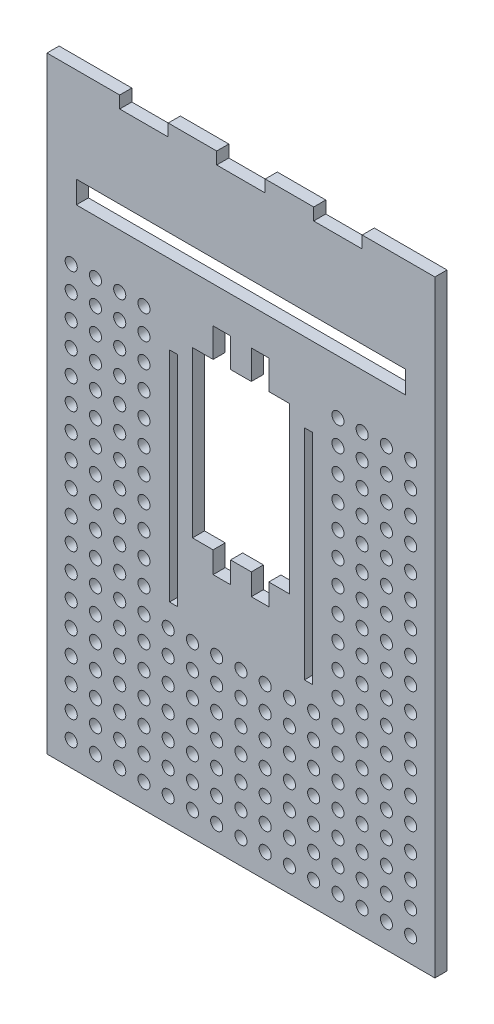
SolidWorks part; units mm, degrees
ref_plane "Front Plane" through (0, 0, 0) normal (0, 0, 1) x (1, 0, 0)
ref_plane "Top Plane" through (0, 0, 0) normal (0, 1, 0) x (1, 0, 0)
ref_plane "Right Plane" through (0, 0, 0) normal (1, 0, 0) x (0, 0, -1)
sketch "Sketch1" plane through (0, 0, 0) normal (0, 0, 1) x (1, 0, 0)
  line L1 (50.8, -79.502) -> (-50.8, -79.502)
  line L2 (50.8, -79.502) -> (50.8, 79.502)
  line L3 (50.8, 79.502) -> (-50.8, 79.502)
  line L4 (-50.8, -79.502) -> (-50.8, 79.502)
  line L5 (50.8, -79.502) -> (-50.8, 79.502) construction
  line L6 (50.8, 79.502) -> (-50.8, -79.502) construction
  point P0 (0, 0)
  dimension "D1" = 101.6
  dimension "D2" = 79.502
extrude "Boss-Extrude1" add sketch "Sketch1" along normal blind 3.175
ref_axis "Axis1" through (0, 0, 0) along (0, 0, 1)
sketch "Sketch3" plane through (0, 0, 3.175) normal (0, 0, 1) x (1, 0, 0)
  line L1 (-12.7, 31.75) -> (12.7, 31.75)
  line L2 (-12.7, 31.75) -> (-12.7, -11.43)
  line L3 (-12.7, -11.43) -> (12.7, -11.43)
  line L4 (12.7, 31.75) -> (12.7, -11.43)
  point P4 (0, 31.75)
  dimension "D1" = 25.4
  dimension "D2" = 11.43
  dimension "D3" = 31.75
extrude "Cut-Extrude1" cut sketch "Sketch3" against normal up to next
sketch "Sketch4" plane through (0, 0, 3.175) normal (0, 0, 1) x (1, 0, 0)
  line L1 (-6.35, 76.327) -> (6.35, 76.327)
  line L2 (-6.35, 76.327) -> (-6.35, 79.502)
  line L3 (-6.35, 79.502) -> (6.35, 79.502)
  line L4 (6.35, 76.327) -> (6.35, 79.502)
  line L5 (19.05, 79.502) -> (31.75, 79.502)
  line L6 (19.05, 76.327) -> (19.05, 79.502)
  line L7 (19.05, 76.327) -> (31.75, 76.327)
  line L8 (31.75, 76.327) -> (31.75, 79.502)
  line L17 (0, -1.7463) -> (0, 1.7463) construction
  line L18 (-31.75, 76.327) -> (-31.75, 79.502)
  line L19 (-19.05, 76.327) -> (-31.75, 76.327)
  line L20 (-19.05, 76.327) -> (-19.05, 79.502)
  line L21 (-19.05, 79.502) -> (-31.75, 79.502)
  line L22 (50.8, 79.502) -> (-50.8, 79.502) construction
  point P6 (0, 79.502)
  point P18 (0, 0)
  dimension "D1" = 3.175
  dimension "D2" = 12.7
  dimension "D3" = 2
  dimension "D4" = 1
extrude "Cut-Extrude2" cut sketch "Sketch4" against normal up to next
sketch "Sketch5" plane through (0, 0, 3.175) normal (0, 0, 1) x (1, 0, 0)
  line L1 (-7.286, 39.37) -> (-2.714, 39.37)
  line L2 (-7.286, 39.37) -> (-7.286, 31.75)
  line L3 (-7.286, 31.75) -> (-2.714, 31.75)
  line L4 (-2.714, 39.37) -> (-2.714, 31.75)
  line L5 (12.7, 31.75) -> (-12.7, 31.75) construction
  line L6 (0, -1.7463) -> (0, 1.7463) construction
  line L7 (2.714, 39.37) -> (2.714, 31.75)
  line L8 (7.286, 31.75) -> (2.714, 31.75)
  line L9 (7.286, 39.37) -> (7.286, 31.75)
  line L10 (7.286, 39.37) -> (2.714, 39.37)
  line L11 (-12.7, -11.43) -> (12.7, -11.43) construction
  line L12 (-7.286, -11.43) -> (-2.714, -11.43)
  line L13 (-7.286, -11.43) -> (-7.286, -17.0574)
  line L14 (-7.286, -17.0574) -> (-2.714, -17.0574)
  line L15 (-2.714, -11.43) -> (-2.714, -17.0574)
  line L16 (0, -52.7486) -> (0, 52.7486) construction
  line L17 (2.714, -11.43) -> (2.714, -17.0574)
  line L18 (7.286, -17.0574) -> (2.714, -17.0574)
  line L19 (7.286, -11.43) -> (7.286, -17.0574)
  line L20 (7.286, -11.43) -> (2.714, -11.43)
  arc A0 (-17.0133, 2.9779) -> (17.0133, 2.9779) centre (0, 0) ccw construction
  point P5 (-5, 39.37)
  dimension "D1" = 4.572
  dimension "D2" = 7.62
extrude "Cut-Extrude3" cut sketch "Sketch5" against normal up to next
sketch "Sketch6" plane through (0, 0, 3.175) normal (0, 0, 1) x (1, 0, 0)
  line L5 (-31.75, 79.502) -> (-50.8, 79.502) construction
  line L6 (-43.1171, 54.737) -> (43.1171, 54.737)
  line L7 (-43.1171, 54.737) -> (-43.1171, 48.895)
  line L8 (-43.1171, 48.895) -> (43.1171, 48.895)
  line L9 (43.1171, 54.737) -> (43.1171, 48.895)
  point P0 (0, 54.737)
  point P13 (-43.1171, 51.816)
  dimension "D1" = 5.842
  dimension "D2" = 86.2342
  dimension "D3" = 27.686
extrude "Cut-Extrude4" cut sketch "Sketch6" against normal up to next
sketch "Sketch7" plane through (0, 0, 3.175) normal (0, 0, 1) x (1, 0, 0)
  line L0 (-50.8, -1.27) -> (50.8, -1.27) construction
  line L1 (-50.8, 79.502) -> (-50.8, -79.502) construction
  line L2 (50.8, -79.502) -> (50.8, 79.502) construction
  line L3 (-31.75, 79.502) -> (-50.8, 79.502) construction
  dimension "D1" = 80.772
ref_plane "Plane1" through (0, -1.27, 0) normal (0, -1, 0) x (1, 0, 0)
sketch "Sketch8" plane through (0, 0, 3.175) normal (0, 0, 1) x (1, 0, 0)
  line L0 (-20.32, 28.2222) -> (20.32, 28.2222) construction
  line L1 (-16.624, -28.9767) -> (-18.7068, -28.9767)
  line L2 (-16.624, -28.9767) -> (-16.624, 28.2222)
  line L3 (-16.624, 28.2222) -> (-18.7068, 28.2222)
  line L4 (-18.7068, -28.9767) -> (-18.7068, 28.2222)
  line L5 (-16.624, -28.9767) -> (-18.7068, 28.2222) construction
  line L6 (-16.624, 28.2222) -> (-18.7068, -28.9767) construction
  line L7 (-14.846, -6.5532) -> (-14.846, 23.5712) construction
  line L8 (0, -1.7463) -> (0, 1.7463) construction
  line L9 (16.624, 28.2222) -> (18.7068, -28.9767) construction
  line L10 (16.624, -28.9767) -> (18.7068, 28.2222) construction
  line L11 (18.7068, -28.9767) -> (18.7068, 28.2222)
  line L12 (16.624, 28.2222) -> (18.7068, 28.2222)
  line L13 (16.624, -28.9767) -> (16.624, 28.2222)
  line L14 (16.624, -28.9767) -> (18.7068, -28.9767)
  point P0 (-17.6654, -0.3772)
  point P7 (0, 0)
  point P8 (-17.6654, 28.2222)
  point P17 (17.6654, 28.2222)
  point P18 (17.6654, -0.3772)
  dimension "D1" = 2.0828
  dimension "D2" = 57.1989
  dimension "D3" = 1.778
extrude "Cut-Extrude5" cut sketch "Sketch8" against normal up to next
sketch "Sketch9" plane through (0, 0, 3.175) normal (0, 0, 1) x (1, 0, 0)
  line L0 (-50.8, -79.502) -> (50.8, -79.502) construction
  line L1 (-50.8, 79.502) -> (-50.8, -79.502) construction
  circle A0 centre (-44.45, -73.152) radius 1.5875
  circle A1 centre (-38.1, -73.152) radius 1.5875
  circle A2 centre (-31.75, -73.152) radius 1.5875
  circle A3 centre (-25.4, -73.152) radius 1.5875
  circle A4 centre (-19.05, -73.152) radius 1.5875
  circle A5 centre (-12.7, -73.152) radius 1.5875
  circle A6 centre (-6.35, -73.152) radius 1.5875
  circle A7 centre (0, -73.152) radius 1.5875
  circle A8 centre (6.35, -73.152) radius 1.5875
  circle A9 centre (12.7, -73.152) radius 1.5875
  circle A10 centre (19.05, -73.152) radius 1.5875
  circle A11 centre (25.4, -73.152) radius 1.5875
  circle A12 centre (31.75, -73.152) radius 1.5875
  circle A13 centre (38.1, -73.152) radius 1.5875
  circle A14 centre (44.45, -73.152) radius 1.5875
  circle A15 centre (-38.1, -66.802) radius 1.5875
  circle A16 centre (-31.75, -66.802) radius 1.5875
  circle A17 centre (-25.4, -66.802) radius 1.5875
  circle A18 centre (-19.05, -66.802) radius 1.5875
  circle A19 centre (-12.7, -66.802) radius 1.5875
  circle A20 centre (-6.35, -66.802) radius 1.5875
  circle A21 centre (0, -66.802) radius 1.5875
  circle A22 centre (6.35, -66.802) radius 1.5875
  circle A23 centre (12.7, -66.802) radius 1.5875
  circle A24 centre (19.05, -66.802) radius 1.5875
  circle A25 centre (25.4, -66.802) radius 1.5875
  circle A26 centre (31.75, -66.802) radius 1.5875
  circle A27 centre (38.1, -66.802) radius 1.5875
  circle A28 centre (44.45, -66.802) radius 1.5875
  circle A29 centre (-38.1, -60.452) radius 1.5875
  circle A30 centre (-31.75, -60.452) radius 1.5875
  circle A31 centre (-25.4, -60.452) radius 1.5875
  circle A32 centre (-19.05, -60.452) radius 1.5875
  circle A33 centre (-12.7, -60.452) radius 1.5875
  circle A34 centre (-6.35, -60.452) radius 1.5875
  circle A35 centre (0, -60.452) radius 1.5875
  circle A36 centre (6.35, -60.452) radius 1.5875
  circle A37 centre (12.7, -60.452) radius 1.5875
  circle A38 centre (19.05, -60.452) radius 1.5875
  circle A39 centre (25.4, -60.452) radius 1.5875
  circle A40 centre (31.75, -60.452) radius 1.5875
  circle A41 centre (38.1, -60.452) radius 1.5875
  circle A42 centre (44.45, -60.452) radius 1.5875
  circle A43 centre (-38.1, -54.102) radius 1.5875
  circle A44 centre (-31.75, -54.102) radius 1.5875
  circle A45 centre (-25.4, -54.102) radius 1.5875
  circle A46 centre (-19.05, -54.102) radius 1.5875
  circle A47 centre (-12.7, -54.102) radius 1.5875
  circle A48 centre (-6.35, -54.102) radius 1.5875
  circle A49 centre (0, -54.102) radius 1.5875
  circle A50 centre (6.35, -54.102) radius 1.5875
  circle A51 centre (12.7, -54.102) radius 1.5875
  circle A52 centre (19.05, -54.102) radius 1.5875
  circle A53 centre (25.4, -54.102) radius 1.5875
  circle A54 centre (31.75, -54.102) radius 1.5875
  circle A55 centre (38.1, -54.102) radius 1.5875
  circle A56 centre (44.45, -54.102) radius 1.5875
  circle A57 centre (-38.1, -47.752) radius 1.5875
  circle A58 centre (-31.75, -47.752) radius 1.5875
  circle A59 centre (-25.4, -47.752) radius 1.5875
  circle A60 centre (-19.05, -47.752) radius 1.5875
  circle A61 centre (-12.7, -47.752) radius 1.5875
  circle A62 centre (-6.35, -47.752) radius 1.5875
  circle A63 centre (0, -47.752) radius 1.5875
  circle A64 centre (6.35, -47.752) radius 1.5875
  circle A65 centre (12.7, -47.752) radius 1.5875
  circle A66 centre (19.05, -47.752) radius 1.5875
  circle A67 centre (25.4, -47.752) radius 1.5875
  circle A68 centre (31.75, -47.752) radius 1.5875
  circle A69 centre (38.1, -47.752) radius 1.5875
  circle A70 centre (44.45, -47.752) radius 1.5875
  circle A71 centre (-38.1, -41.402) radius 1.5875
  circle A72 centre (-31.75, -41.402) radius 1.5875
  circle A73 centre (-25.4, -41.402) radius 1.5875
  circle A74 centre (-19.05, -41.402) radius 1.5875
  circle A75 centre (-12.7, -41.402) radius 1.5875
  circle A76 centre (-6.35, -41.402) radius 1.5875
  circle A77 centre (0, -41.402) radius 1.5875
  circle A78 centre (6.35, -41.402) radius 1.5875
  circle A79 centre (12.7, -41.402) radius 1.5875
  circle A80 centre (19.05, -41.402) radius 1.5875
  circle A81 centre (25.4, -41.402) radius 1.5875
  circle A82 centre (31.75, -41.402) radius 1.5875
  circle A83 centre (38.1, -41.402) radius 1.5875
  circle A84 centre (44.45, -41.402) radius 1.5875
  circle A85 centre (-38.1, -35.052) radius 1.5875
  circle A86 centre (-31.75, -35.052) radius 1.5875
  circle A87 centre (-25.4, -35.052) radius 1.5875
  circle A88 centre (-19.05, -35.052) radius 1.5875
  circle A89 centre (-12.7, -35.052) radius 1.5875
  circle A90 centre (-6.35, -35.052) radius 1.5875
  circle A91 centre (0, -35.052) radius 1.5875
  circle A92 centre (6.35, -35.052) radius 1.5875
  circle A93 centre (12.7, -35.052) radius 1.5875
  circle A94 centre (19.05, -35.052) radius 1.5875
  circle A95 centre (25.4, -35.052) radius 1.5875
  circle A96 centre (31.75, -35.052) radius 1.5875
  circle A97 centre (38.1, -35.052) radius 1.5875
  circle A98 centre (44.45, -35.052) radius 1.5875
  circle A99 centre (-44.45, -66.802) radius 1.5875
  circle A100 centre (-44.45, -60.452) radius 1.5875
  circle A101 centre (-44.45, -54.102) radius 1.5875
  circle A102 centre (-44.45, -47.752) radius 1.5875
  circle A103 centre (-44.45, -41.402) radius 1.5875
  circle A104 centre (-44.45, -35.052) radius 1.5875
  circle A105 centre (-44.45, -28.702) radius 1.5875
  circle A106 centre (-38.1, -28.702) radius 1.5875
  circle A107 centre (-31.75, -28.702) radius 1.5875
  circle A108 centre (-25.4, -28.702) radius 1.5875
  circle A116 centre (25.4, -28.702) radius 1.5875
  circle A117 centre (31.75, -28.702) radius 1.5875
  circle A118 centre (38.1, -28.702) radius 1.5875
  circle A119 centre (44.45, -28.702) radius 1.5875
  circle A120 centre (-44.45, -22.352) radius 1.5875
  circle A121 centre (-38.1, -22.352) radius 1.5875
  circle A122 centre (-31.75, -22.352) radius 1.5875
  circle A123 centre (-25.4, -22.352) radius 1.5875
  circle A131 centre (25.4, -22.352) radius 1.5875
  circle A132 centre (31.75, -22.352) radius 1.5875
  circle A133 centre (38.1, -22.352) radius 1.5875
  circle A134 centre (44.45, -22.352) radius 1.5875
  circle A135 centre (-44.45, -16.002) radius 1.5875
  circle A136 centre (-38.1, -16.002) radius 1.5875
  circle A137 centre (-31.75, -16.002) radius 1.5875
  circle A138 centre (-25.4, -16.002) radius 1.5875
  circle A146 centre (25.4, -16.002) radius 1.5875
  circle A147 centre (31.75, -16.002) radius 1.5875
  circle A148 centre (38.1, -16.002) radius 1.5875
  circle A149 centre (44.45, -16.002) radius 1.5875
  circle A150 centre (-44.45, -9.652) radius 1.5875
  circle A151 centre (-38.1, -9.652) radius 1.5875
  circle A152 centre (-31.75, -9.652) radius 1.5875
  circle A153 centre (-25.4, -9.652) radius 1.5875
  circle A161 centre (25.4, -9.652) radius 1.5875
  circle A162 centre (31.75, -9.652) radius 1.5875
  circle A163 centre (38.1, -9.652) radius 1.5875
  circle A164 centre (44.45, -9.652) radius 1.5875
  circle A165 centre (-44.45, -3.302) radius 1.5875
  circle A166 centre (-38.1, -3.302) radius 1.5875
  circle A167 centre (-31.75, -3.302) radius 1.5875
  circle A168 centre (-25.4, -3.302) radius 1.5875
  circle A176 centre (25.4, -3.302) radius 1.5875
  circle A177 centre (31.75, -3.302) radius 1.5875
  circle A178 centre (38.1, -3.302) radius 1.5875
  circle A179 centre (44.45, -3.302) radius 1.5875
  circle A180 centre (-44.45, 3.048) radius 1.5875
  circle A181 centre (-38.1, 3.048) radius 1.5875
  circle A182 centre (-31.75, 3.048) radius 1.5875
  circle A183 centre (-25.4, 3.048) radius 1.5875
  circle A191 centre (25.4, 3.048) radius 1.5875
  circle A192 centre (31.75, 3.048) radius 1.5875
  circle A193 centre (38.1, 3.048) radius 1.5875
  circle A194 centre (44.45, 3.048) radius 1.5875
  circle A195 centre (-44.45, 9.398) radius 1.5875
  circle A196 centre (-38.1, 9.398) radius 1.5875
  circle A197 centre (-31.75, 9.398) radius 1.5875
  circle A198 centre (-25.4, 9.398) radius 1.5875
  circle A206 centre (25.4, 9.398) radius 1.5875
  circle A207 centre (31.75, 9.398) radius 1.5875
  circle A208 centre (38.1, 9.398) radius 1.5875
  circle A209 centre (44.45, 9.398) radius 1.5875
  circle A210 centre (-44.45, 15.748) radius 1.5875
  circle A211 centre (-38.1, 15.748) radius 1.5875
  circle A212 centre (-31.75, 15.748) radius 1.5875
  circle A213 centre (-25.4, 15.748) radius 1.5875
  circle A221 centre (25.4, 15.748) radius 1.5875
  circle A222 centre (31.75, 15.748) radius 1.5875
  circle A223 centre (38.1, 15.748) radius 1.5875
  circle A224 centre (44.45, 15.748) radius 1.5875
  circle A225 centre (-44.45, 22.098) radius 1.5875
  circle A226 centre (-38.1, 22.098) radius 1.5875
  circle A227 centre (-31.75, 22.098) radius 1.5875
  circle A228 centre (-25.4, 22.098) radius 1.5875
  circle A236 centre (25.4, 22.098) radius 1.5875
  circle A237 centre (31.75, 22.098) radius 1.5875
  circle A238 centre (38.1, 22.098) radius 1.5875
  circle A239 centre (44.45, 22.098) radius 1.5875
  circle A240 centre (-44.45, 28.448) radius 1.5875
  circle A241 centre (-38.1, 28.448) radius 1.5875
  circle A242 centre (-31.75, 28.448) radius 1.5875
  circle A243 centre (-25.4, 28.448) radius 1.5875
  circle A251 centre (25.4, 28.448) radius 1.5875
  circle A252 centre (31.75, 28.448) radius 1.5875
  circle A253 centre (38.1, 28.448) radius 1.5875
  circle A254 centre (44.45, 28.448) radius 1.5875
  circle A255 centre (-44.45, 34.798) radius 1.5875
  circle A256 centre (-38.1, 34.798) radius 1.5875
  circle A257 centre (-31.75, 34.798) radius 1.5875
  circle A258 centre (-25.4, 34.798) radius 1.5875
  circle A266 centre (25.4, 34.798) radius 1.5875
  circle A267 centre (31.75, 34.798) radius 1.5875
  circle A268 centre (38.1, 34.798) radius 1.5875
  circle A269 centre (44.45, 34.798) radius 1.5875
  circle A285 centre (-19.05, -28.702) radius 1.5875 [skipped]
  circle A286 centre (-12.7, -28.702) radius 1.5875 [skipped]
  circle A287 centre (-6.35, -28.702) radius 1.5875 [skipped]
  circle A288 centre (0, -28.702) radius 1.5875 [skipped]
  circle A289 centre (6.35, -28.702) radius 1.5875 [skipped]
  circle A290 centre (12.7, -28.702) radius 1.5875 [skipped]
  circle A291 centre (19.05, -28.702) radius 1.5875 [skipped]
  circle A292 centre (-19.05, -22.352) radius 1.5875 [skipped]
  circle A293 centre (-12.7, -22.352) radius 1.5875 [skipped]
  circle A294 centre (-6.35, -22.352) radius 1.5875 [skipped]
  circle A295 centre (0, -22.352) radius 1.5875 [skipped]
  circle A296 centre (6.35, -22.352) radius 1.5875 [skipped]
  circle A297 centre (12.7, -22.352) radius 1.5875 [skipped]
  circle A298 centre (19.05, -22.352) radius 1.5875 [skipped]
  circle A299 centre (-19.05, -16.002) radius 1.5875 [skipped]
  circle A300 centre (-12.7, -16.002) radius 1.5875 [skipped]
  circle A301 centre (-6.35, -16.002) radius 1.5875 [skipped]
  circle A302 centre (0, -16.002) radius 1.5875 [skipped]
  circle A303 centre (6.35, -16.002) radius 1.5875 [skipped]
  circle A304 centre (12.7, -16.002) radius 1.5875 [skipped]
  circle A305 centre (19.05, -16.002) radius 1.5875 [skipped]
  circle A306 centre (-19.05, -9.652) radius 1.5875 [skipped]
  circle A307 centre (-12.7, -9.652) radius 1.5875 [skipped]
  circle A308 centre (-6.35, -9.652) radius 1.5875 [skipped]
  circle A309 centre (0, -9.652) radius 1.5875 [skipped]
  circle A310 centre (6.35, -9.652) radius 1.5875 [skipped]
  circle A311 centre (12.7, -9.652) radius 1.5875 [skipped]
  circle A312 centre (19.05, -9.652) radius 1.5875 [skipped]
  circle A313 centre (-19.05, -3.302) radius 1.5875 [skipped]
  circle A314 centre (-12.7, -3.302) radius 1.5875 [skipped]
  circle A315 centre (-6.35, -3.302) radius 1.5875 [skipped]
  circle A316 centre (0, -3.302) radius 1.5875 [skipped]
  circle A317 centre (6.35, -3.302) radius 1.5875 [skipped]
  circle A318 centre (12.7, -3.302) radius 1.5875 [skipped]
  circle A319 centre (19.05, -3.302) radius 1.5875 [skipped]
  circle A320 centre (-19.05, 3.048) radius 1.5875 [skipped]
  circle A321 centre (-12.7, 3.048) radius 1.5875 [skipped]
  circle A322 centre (-6.35, 3.048) radius 1.5875 [skipped]
  circle A323 centre (0, 3.048) radius 1.5875 [skipped]
  circle A324 centre (6.35, 3.048) radius 1.5875 [skipped]
  circle A325 centre (12.7, 3.048) radius 1.5875 [skipped]
  circle A326 centre (19.05, 3.048) radius 1.5875 [skipped]
  circle A327 centre (-19.05, 9.398) radius 1.5875 [skipped]
  circle A328 centre (-12.7, 9.398) radius 1.5875 [skipped]
  circle A329 centre (-6.35, 9.398) radius 1.5875 [skipped]
  circle A330 centre (0, 9.398) radius 1.5875 [skipped]
  circle A331 centre (6.35, 9.398) radius 1.5875 [skipped]
  circle A332 centre (12.7, 9.398) radius 1.5875 [skipped]
  circle A333 centre (19.05, 9.398) radius 1.5875 [skipped]
  circle A334 centre (-19.05, 15.748) radius 1.5875 [skipped]
  circle A335 centre (-12.7, 15.748) radius 1.5875 [skipped]
  circle A336 centre (-6.35, 15.748) radius 1.5875 [skipped]
  circle A337 centre (0, 15.748) radius 1.5875 [skipped]
  circle A338 centre (6.35, 15.748) radius 1.5875 [skipped]
  circle A339 centre (12.7, 15.748) radius 1.5875 [skipped]
  circle A340 centre (19.05, 15.748) radius 1.5875 [skipped]
  circle A341 centre (-19.05, 22.098) radius 1.5875 [skipped]
  circle A342 centre (-12.7, 22.098) radius 1.5875 [skipped]
  circle A343 centre (-6.35, 22.098) radius 1.5875 [skipped]
  circle A344 centre (0, 22.098) radius 1.5875 [skipped]
  circle A345 centre (6.35, 22.098) radius 1.5875 [skipped]
  circle A346 centre (12.7, 22.098) radius 1.5875 [skipped]
  circle A347 centre (19.05, 22.098) radius 1.5875 [skipped]
  circle A348 centre (-19.05, 28.448) radius 1.5875 [skipped]
  circle A349 centre (-12.7, 28.448) radius 1.5875 [skipped]
  circle A350 centre (-6.35, 28.448) radius 1.5875 [skipped]
  circle A351 centre (0, 28.448) radius 1.5875 [skipped]
  circle A352 centre (6.35, 28.448) radius 1.5875 [skipped]
  circle A353 centre (12.7, 28.448) radius 1.5875 [skipped]
  circle A354 centre (19.05, 28.448) radius 1.5875 [skipped]
  circle A355 centre (-19.05, 34.798) radius 1.5875 [skipped]
  circle A356 centre (-12.7, 34.798) radius 1.5875 [skipped]
  circle A357 centre (-6.35, 34.798) radius 1.5875 [skipped]
  circle A358 centre (0, 34.798) radius 1.5875 [skipped]
  circle A359 centre (6.35, 34.798) radius 1.5875 [skipped]
  circle A360 centre (12.7, 34.798) radius 1.5875 [skipped]
  circle A361 centre (19.05, 34.798) radius 1.5875 [skipped]
  circle A362 centre (-19.05, 41.148) radius 1.5875 [skipped]
  circle A363 centre (-12.7, 41.148) radius 1.5875 [skipped]
  circle A364 centre (-6.35, 41.148) radius 1.5875 [skipped]
  circle A365 centre (0, 41.148) radius 1.5875 [skipped]
  circle A366 centre (6.35, 41.148) radius 1.5875 [skipped]
  circle A367 centre (12.7, 41.148) radius 1.5875 [skipped]
  circle A368 centre (19.05, 41.148) radius 1.5875 [skipped]
  circle A369 centre (-44.45, 41.148) radius 1.5875 [skipped]
  circle A370 centre (-38.1, 41.148) radius 1.5875 [skipped]
  circle A371 centre (-31.75, 41.148) radius 1.5875 [skipped]
  circle A372 centre (-25.4, 41.148) radius 1.5875 [skipped]
  circle A373 centre (25.4, 41.148) radius 1.5875 [skipped]
  circle A374 centre (31.75, 41.148) radius 1.5875 [skipped]
  circle A375 centre (38.1, 41.148) radius 1.5875 [skipped]
  circle A376 centre (44.45, 41.148) radius 1.5875 [skipped]
  dimension "D1" = 3.175
  dimension "D2" = 6.35
  dimension "D3" = 6.35
  dimension "D4" = 15
  dimension "D5" = 19
extrude "Cut-Extrude6" cut sketch "Sketch9" against normal up to next (3.175 mm away)
